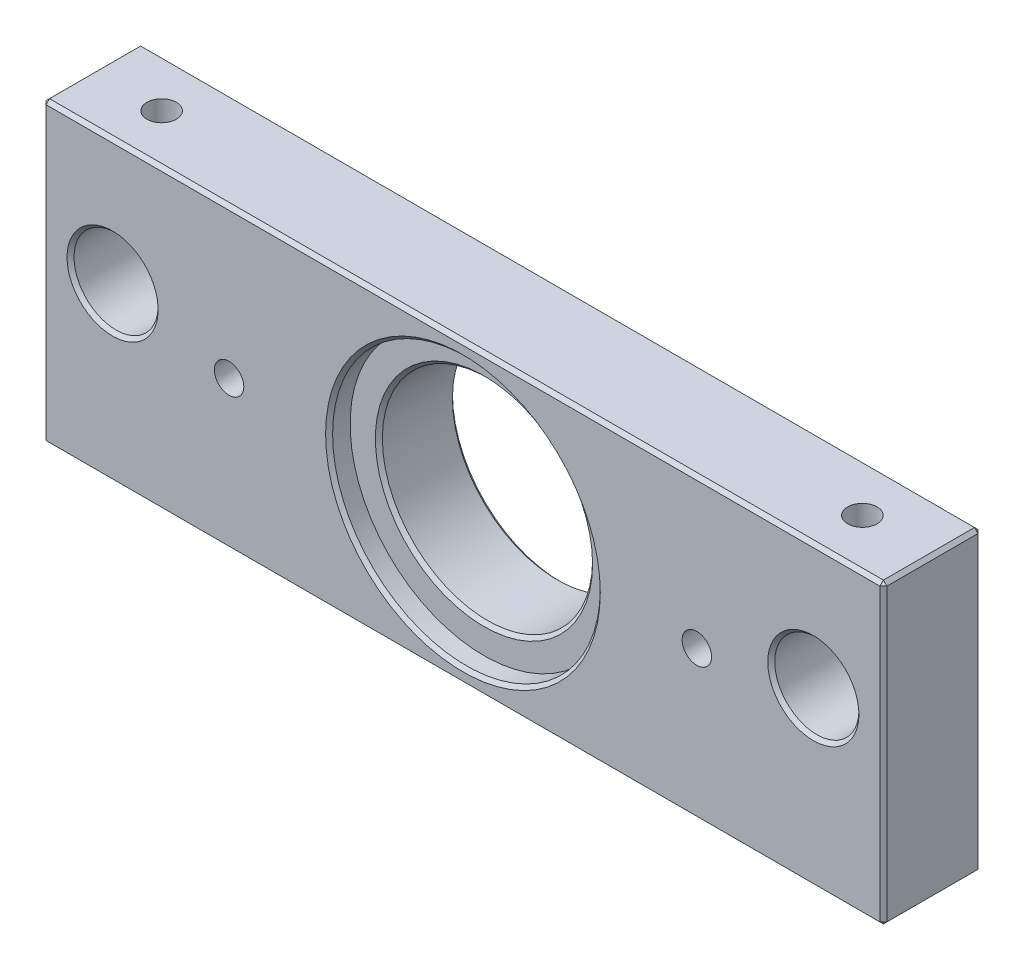
SolidWorks part; units mm, degrees
ref_plane "Front Plane" through (0, 0, 0) normal (0, 0, 1) x (1, 0, 0)
ref_plane "Top Plane" through (0, 0, 0) normal (0, 1, 0) x (1, 0, 0)
ref_plane "Right Plane" through (0, 0, 0) normal (1, 0, 0) x (0, 0, -1)
sketch "Sketch1" plane through (0, 0, 0) normal (0, 0, 1) x (1, 0, 0)
  line L1 (-60, -21.25) -> (60, -21.25)
  line L2 (-60, -21.25) -> (-60, 21.25)
  line L3 (-60, 21.25) -> (60, 21.25)
  line L4 (60, -21.25) -> (60, 21.25)
  line L5 (-60, -21.25) -> (60, 21.25) construction
  line L6 (-60, 21.25) -> (60, -21.25) construction
  point P0 (0, 0)
  dimension "D1" = 120
  dimension "D2" = 42.5
extrude "Boss-Extrude1" add sketch "Sketch1" along normal mid plane 14
sketch "Sketch2" plane through (0, 0, 7) normal (0, 0, 1) x (1, 0, 0)
  circle A0 centre (0, 0) radius 19.1
  dimension "D1" = 38.2
extrude "Cut-Extrude1" cut sketch "Sketch2" against normal blind 3
sketch "Sketch3" plane through (0, 0, 4) normal (0, 0, 1) x (1, 0, 0)
  circle A0 centre (0, 0) radius 15
extrude "Cut-Extrude2" cut sketch "Sketch3" against normal through all
hole_wizard "M5x0.8 Tapped Hole3" positions "Sketch13" profile "Sketch12" tap size "M5x0.8" standard "ANSI Metric"
sketch "Sketch13" plane through (0, 0, 7) normal (0, 0, 1) x (1, 0, 0)
  line L0 (-1000, 0) -> (49000, 0) construction
  point P0 (-33.375, 0)
  point P2 (33.375, 0)
  dimension "D1" = 33.375
  dimension "D2" = 33.375
sketch "Sketch12" plane through (-33.375, 0, 7) normal (1, 0, 0) x (0, -1, 0)
  line L0 (0, 0) -> (0, 15.2618)
  line L1 (0, 15.2618) -> (2.1, 14)
  line L2 (2.1, 14) -> (2.1, 0)
  line L5 (2.1, 0) -> (0, 0)
  line L10 (0, 15.2618) -> (-2.1, 14) construction
  line L11 (0, -6.35) -> (0, 107.95) construction
  dimension "Tap Drill Dia." = 4.2
  dimension "Tap Drill Depth" = 14
  dimension "Drill Angle" = 118
cosmetic thread "Hole Thread6" parameters "D1"=10, "D2"=5
cosmetic thread "Hole Thread7" parameters "D1"=10, "D2"=5
sketch "Sketch5" plane through (0, 0, 7) normal (0, 0, 1) x (1, 0, 0)
  line L0 (-40.6477, 3.4) -> (36.4799, 3.4) construction
  circle A0 centre (-50, 3.4) radius 6
  circle A1 centre (50, 3.4) radius 6
  dimension "D1" = 12
  dimension "D2" = 12
  dimension "D4" = 50
  dimension "D3" = 50
  dimension "D5" = 3.4
extrude "Cut-Extrude4" cut sketch "Sketch5" against normal through all
hole_wizard "M5x0.8 Tapped Hole2" positions "Sketch11" profile "Sketch10" tap size "M5x0.8" standard "ANSI Metric"
sketch "Sketch11" plane through (0, -21.25, 0) normal (0, -1, 0) x (-1, 0, 0)
  line L0 (-1000, 0) -> (49000, 0) construction
  line L1 (60, -7) -> (60, 7) construction
  point P0 (50, 0)
  point P4 (25, 0)
  dimension "D1" = 10
  dimension "D2" = 35
sketch "Sketch10" plane through (-50, -21.25, 0) normal (1, 0, 0) x (0, 0, -1)
  line L0 (0, 0) -> (0, 15.2618)
  line L1 (0, 15.2618) -> (2.1, 14)
  line L2 (2.1, 14) -> (2.1, 0)
  line L5 (2.1, 0) -> (0, 0)
  line L10 (0, 15.2618) -> (-2.1, 14) construction
  line L11 (0, -6.35) -> (0, 107.95) construction
  dimension "Tap Drill Dia." = 4.2
  dimension "Tap Drill Depth" = 14
  dimension "Drill Angle" = 118
cosmetic thread "Hole Thread3" parameters "D1"=10, "D2"=5
cosmetic thread "Hole Thread5" parameters "D1"=10, "D2"=5
sketch "Sketch6" plane through (0, -21.25, 0) normal (0, -1, 0) x (1, 0, 0)
  line L0 (-60, 0) -> (60, 0) construction
  line L1 (-60, 7) -> (-60, -7) construction
  line L2 (60, 7) -> (60, -7) construction
  circle A4 centre (-37.5, 0) radius 1.25
  dimension "D9" = 2.5
  dimension "D11" = 22.5
extrude "Cut-Extrude5" cut sketch "Sketch6" against normal blind 10
mirror "Mirror1" about plane through (0, 0, 0) normal (1, 0, 0) of "Cut-Extrude5", "M5x0.8 Tapped Hole2"
hole_wizard "M5x0.8 Tapped Hole1" positions "Sketch9" profile "Sketch8" tap size "M5x0.8" standard "ANSI Metric" end condition up to next
sketch "Sketch9" plane through (0, 21.25, 0) normal (0, 1, 0) x (1, 0, 0)
  line L0 (-1000, 0) -> (49000, 0) construction
  line L1 (-60, -7) -> (-60, 7) construction
  line L2 (60, -7) -> (60, 7) construction
  point P0 (-50, 0)
  point P3 (50, 0)
  dimension "D1" = 10
  dimension "D2" = 10
sketch "Sketch8" plane through (-50, 21.25, 0) normal (1, 0, 0) x (0, 0, 1)
  line L0 (0, 0) -> (0, 11.85)
  line L1 (0, 11.85) -> (2.1, 11.85)
  line L2 (2.1, 11.85) -> (2.1, 0)
  line L5 (2.1, 0) -> (0, 0)
  line L11 (0, -6.35) -> (0, 107.95) construction
  dimension "Thru Tap Drill Dia." = 4.2
  dimension "Thru Tap Drill Depth" = 11.85
cosmetic thread "Hole Thread1" parameters "D2"=5
cosmetic thread "Hole Thread2" parameters "D2"=5
chamfer "Chamfer1" distance 0.5 angle 45 21 edges at (-44, 3.4, -7) (56, 3.4, -7) (56, 3.4, 7) (-44, 3.4, 7) (15, 0, -7) (15, 0, 4) (19.1, 0, 7) (-37.5, -21.25, -1.25) (37.5, -21.25, -1.25) (0, -21.25, -7) (60, -21.25, 0) (60, 0, -7) (60, 21.25, 0) (60, 0, 7) (0, -21.25, 7) (-60, -21.25, 0) (-60, 0, -7) (-60, 0, 7) (0, 21.25, -7) (-60, 21.25, 0) (0, 21.25, 7)
equation "\"D1@Sketch13\"=66.75/2"
equation "\"D2@Sketch13\"=66.75/2"
